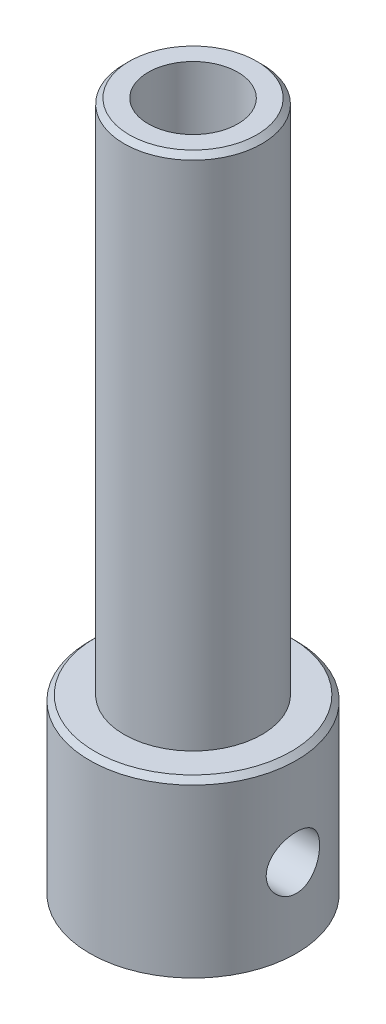
SolidWorks part; units mm, degrees
ref_plane "Front Plane" through (0, 0, 0) normal (0, 0, 1) x (1, 0, 0)
ref_plane "Top Plane" through (0, 0, 0) normal (0, 1, 0) x (1, 0, 0)
ref_plane "Right Plane" through (0, 0, 0) normal (1, 0, 0) x (0, 0, -1)
sketch "Sketch6" plane through (0, 0, 0) normal (0, 1, 0) x (1, 0, 0)
  circle A0 centre (0, 0) radius 6
extrude "Boss-Extrude4" add sketch "Sketch6" along normal blind 10
sketch "Sketch7" plane through (0, 10, 0) normal (0, 1, 0) x (1, 0, 0)
  circle A0 centre (0, 0) radius 4
  dimension "D1" = 8
extrude "Boss-Extrude5" add sketch "Sketch7" along normal blind 30
chamfer "Chamfer1" distance 0.3 angle 45 1 edges at (0, 40, 4)
chamfer "Chamfer2" distance 0.3 angle 45 1 edges at (0, 10, 6)
ref_plane "Plane5" through (-6, 0, 0) normal (-1, 0, 0) x (0, 0, 1)
sketch "Sketch10" plane through (-6, 0, 0) normal (-1, 0, 0) x (0, 0, 1)
  circle A0 centre (0, 4.5671) radius 1.55
extrude "Cut-Extrude4" cut sketch "Sketch10" against normal through all both and the other way through all contours A0
sketch "Sketch11" plane through (0, 40, 0) normal (0, 1, 0) x (1, 0, 0)
  circle A0 centre (0, 0) radius 2.6
  dimension "D1" = 5.2
extrude "Cut-Extrude5" cut sketch "Sketch11" against normal through all and the other way through all
